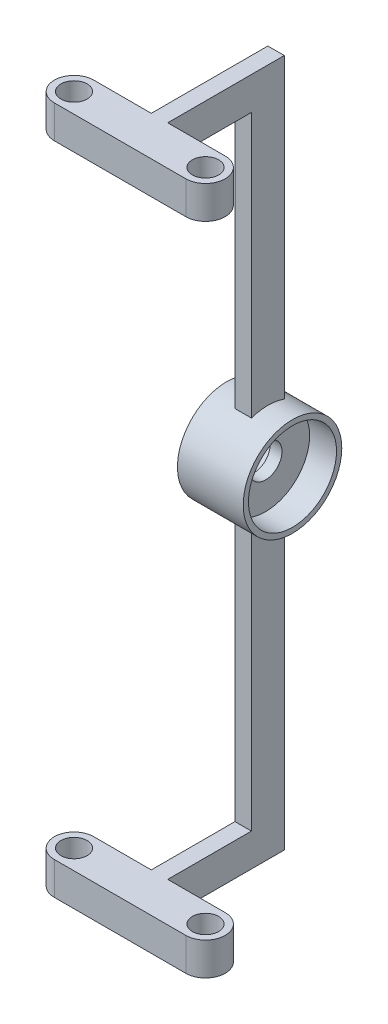
SolidWorks part; units mm, degrees
ref_plane "Front" through (0, 0, 0) normal (0, 0, 1) x (1, 0, 0)
ref_plane "Top" through (0, 0, 0) normal (0, 1, 0) x (1, 0, 0)
ref_plane "Right" through (0, 0, 0) normal (1, 0, 0) x (0, 0, -1)
sketch "Sketch1" plane through (0, 0, 0) normal (1, 0, 0) x (0, 0, -1)
  line L0 (0, 100.9459) -> (0, -99.0541) construction
  line L1 (-11.4058, 104.6846) -> (-11.4058, 94.6846)
  line L2 (-11.4058, 94.6846) -> (26.0619, 94.6846)
  line L3 (-11.4058, 104.6846) -> (36.0619, 104.6846)
  line L4 (-19.0433, 0) -> (30.354, 0) construction
  line L5 (-11.4058, -104.6846) -> (36.0619, -104.6846)
  line L6 (-11.4058, -94.6846) -> (26.0619, -94.6846)
  line L7 (-11.4058, -104.6846) -> (-11.4058, -94.6846)
  line L8 (36.0619, 104.6846) -> (36.0619, -13.4401)
  line L9 (26.0619, 94.6846) -> (26.0619, -94.6846)
  line L10 (36.0619, -13.4401) -> (36.0619, -104.6846)
  dimension "D1" = 200
  dimension "D2" = 10
  dimension "D3" = 10
extrude "Boss-Extrude1" add sketch "Sketch1" along normal mid plane 5
sketch "Sketch2" plane through (0, 104.6846, -93.2787) normal (0, -1, 0) x (1, 0, 0)
  line L0 (-20, 98.6846) -> (20, 98.6846) construction
  line L1 (-20, 104.6846) -> (20, 104.6846)
  line L2 (-20, 92.6846) -> (20, 92.6846)
  line L3 (2.5, 104.6846) -> (-2.5, 104.6846) construction
  line L5 (0, 80.7776) -> (0, 113.4638) construction
  arc A0 (-20, 104.6846) -> (-20, 92.6846) centre (-20, 98.6846) ccw
  arc A1 (20, 92.6846) -> (20, 104.6846) centre (20, 98.6846) ccw
  circle A2 centre (20, 98.6846) radius 4
  circle A3 centre (-20, 98.6846) radius 4
  point P2 (0, 98.6846)
  dimension "D2" = 6
  dimension "D3" = 8
  dimension "D1" = 40
extrude "Boss-Extrude2" add sketch "Sketch2" along normal up to surface (10 mm away) up to face at (0, 94.6846, -7.328)
sketch "Sketch3" plane through (0, -94.6846, 0) normal (0, 1, 0) x (1, 0, 0)
  line L0 (-20, 0.5942) -> (-2.5, 0.5942) construction
  line L1 (2.5, 0.5942) -> (20, 0.5942) construction
  line L2 (20, -11.4058) -> (-20, -11.4058) construction
  line L3 (-20, 0.5942) -> (-2.5, 0.5942)
  line L4 (2.5, 0.5942) -> (20, 0.5942)
  line L5 (20, -11.4058) -> (-20, -11.4058)
  line L6 (2.5, 0.5942) -> (-2.5, 0.5942)
  arc A0 (20, -11.4058) -> (20, 0.5942) centre (20, -5.4058) ccw construction
  circle A1 centre (20, -5.4058) radius 4 construction
  circle A2 centre (-20, -5.4058) radius 4 construction
  arc A3 (-20, 0.5942) -> (-20, -11.4058) centre (-20, -5.4058) ccw construction
  arc A4 (20, -11.4058) -> (20, 0.5942) centre (20, -5.4058) ccw
  circle A5 centre (20, -5.4058) radius 4
  circle A6 centre (-20, -5.4058) radius 4
  arc A7 (-20, 0.5942) -> (-20, -11.4058) centre (-20, -5.4058) ccw
extrude "Boss-Extrude3" add sketch "Sketch3" against normal up to surface (10 mm away) up to face at (0, -104.6846, -12.328)
sketch "Sketch4" plane through (0, 0, 0) normal (1, 0, 0) x (0, 0, -1)
  line L0 (31.0619, 6.4033) -> (31.0619, -4.3005) construction
  line L2 (26.0619, 94.6846) -> (26.0619, -94.6846) construction
  line L3 (36.0619, -104.6846) -> (36.0619, 104.6846) construction
  circle A0 centre (31.0619, 0) radius 15
  dimension "D1" = 30
extrude "Boss-Extrude4" add sketch "Sketch4" along normal mid plane 20 contours A0
sketch "Sketch5" plane through (10, 0, 0) normal (1, 0, 0) x (0, 0, -1)
  circle A0 centre (31.0619, 0) radius 13.4
  circle A1 centre (31.0619, 0) radius 15 construction
  dimension "D1" = 26.8
extrude "Cut-Extrude1" cut sketch "Sketch5" against normal blind 8.2
mirror "Mirror3" about plane through (0, 0, 0) normal (1, 0, 0) of "Cut-Extrude1"
sketch "Sketch6" plane through (1.8, 0, 0) normal (1, 0, 0) x (0, 0, -1)
  circle A0 centre (31.0619, 0) radius 5
  circle A1 centre (31.0619, 0) radius 13.4 construction
  dimension "D1" = 10
extrude "Cut-Extrude2" cut sketch "Sketch6" against normal through all contours A0
